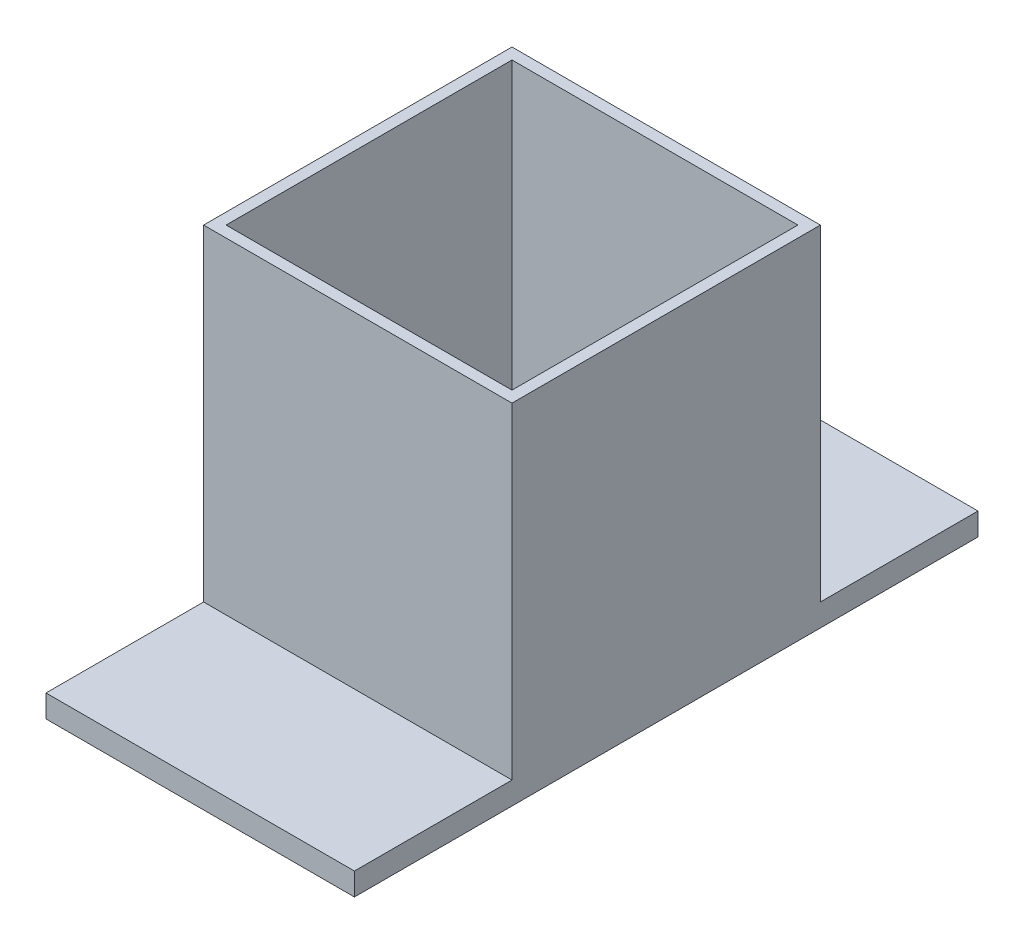
SolidWorks part; units mm, degrees
ref_plane "Front Plane" through (0, 0, 0) normal (0, 0, 1) x (1, 0, 0)
ref_plane "Top Plane" through (0, 0, 0) normal (0, 1, 0) x (1, 0, 0)
ref_plane "Right Plane" through (0, 0, 0) normal (1, 0, 0) x (0, 0, -1)
sketch "Sketch2" plane through (0, 0, 0) normal (0, 1, 0) x (1, 0, 0)
  line L1 (0, 0) -> (13.7, 0)
  line L2 (0, 0) -> (0, 13.7)
  line L3 (0, 13.7) -> (13.7, 13.7)
  line L4 (13.7, 0) -> (13.7, 13.7)
  line L5 (13.7, 0) -> (13.2, 0)
  line L6 (13.7, 0) -> (13.7, 13.7)
  line L7 (13.7, 13.7) -> (13.2, 13.7)
  line L8 (13.2, 0) -> (13.2, 13.7)
  line L9 (13.2, 0) -> (0, 0)
  line L10 (13.2, 0) -> (13.2, 0.5)
  line L11 (13.2, 0.5) -> (0, 0.5)
  line L12 (0, 0) -> (0, 0.5)
  line L13 (0, 0.5) -> (0.5, 0.5)
  line L14 (0, 0.5) -> (0, 13.7)
  line L15 (0, 13.7) -> (0.5, 13.7)
  line L16 (0.5, 0.5) -> (0.5, 13.7)
  line L17 (0.5, 13.7) -> (13.2, 13.7)
  line L18 (0.5, 13.7) -> (0.5, 13.2)
  line L19 (0.5, 13.2) -> (13.2, 13.2)
  line L20 (13.2, 13.7) -> (13.2, 13.2)
  dimension "D1" = 13.7
  dimension "D2" = 13.7
  dimension "D3" = 0.5
  dimension "D4" = 0.5
  dimension "D5" = 0.5
  dimension "D6" = 0.5
extrude "Boss-Extrude2" add sketch "Sketch2" against normal blind 0.5 contours L19 L16 L11 L8 | L8 L1 L4 L3 | L16 L19 L8 L3 | L8 L11 L2 L1 | L11 L16 L3 L2 region at (6.6, 0, -0.25) region at (13.45, 0, -6.85) region at (0.25, 0, -7.1) region at (6.85, 0, -6.85) region at (6.85, 0, -13.45)
extrude "Boss-Extrude3" add sketch "Sketch2<4>" along normal blind 15 contours L11 L16 L3 L2 | L16 L19 L8 L3 | L8 L1 L4 L3 | L8 L11 L2 L1 region at (6.6, 0, -0.25) region at (13.45, 0, -6.85) region at (0.25, 0, -7.1) region at (6.85, 0, -13.45)
sketch "Sketch2<4>" plane through (0, 0, 0) normal (0, 1, 0) x (1, 0, 0) same geometry as "Sketch2"
sketch "Sketch3" plane through (0, 0, 0) normal (0, 0, 1) x (1, 0, 0)
  line L0 (13.7, -0.5) -> (13.7, 15) construction
  line L1 (0, -0.5) -> (13.7, -0.5)
  line L2 (0, -0.5) -> (0, 0.5)
  line L3 (0, 0.5) -> (13.7, 0.5)
  line L4 (13.7, -0.5) -> (13.7, 0.5)
  dimension "D1" = 1
extrude "Boss-Extrude4" add sketch "Sketch3" along normal blind 7
sketch "Sketch4" plane through (0, 0, -13.7) normal (0, 0, -1) x (-1, 0, 0)
  line L0 (0, -0.5) -> (0, 15) construction
  line L1 (-13.7, -0.5) -> (0, -0.5)
  line L2 (-13.7, -0.5) -> (-13.7, 0.5)
  line L3 (-13.7, 0.5) -> (0, 0.5)
  line L4 (0, -0.5) -> (0, 0.5)
  dimension "D1" = 1
extrude "Boss-Extrude6" add sketch "Sketch4" along normal blind 7
